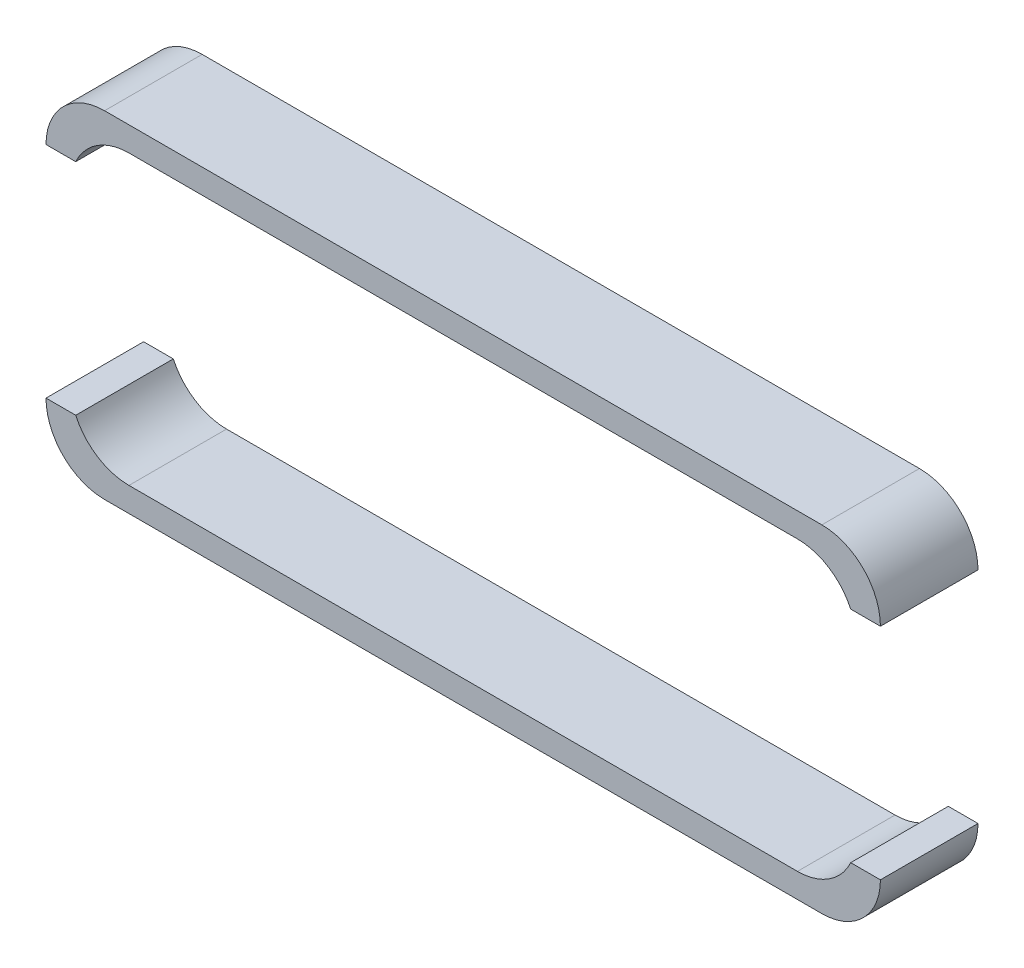
SolidWorks part; units mm, degrees
ref_plane "Plan de face" through (0, 0, 0) normal (0, 0, 1) x (1, 0, 0)
ref_plane "Plan de dessus" through (0, 0, 0) normal (0, 1, 0) x (1, 0, 0)
ref_plane "Plan de droite" through (0, 0, 0) normal (1, 0, 0) x (0, 0, -1)
sketch "Esquisse1" plane through (0, 0, 0) normal (0, 0, 1) x (1, 0, 0)
  line L1 (0, 0) -> (80.5, 0)
  line L2 (0, 0) -> (0, 29.5)
  line L3 (0, 29.5) -> (80.5, 29.5)
  line L4 (80.5, 0) -> (80.5, 29.5)
  line L5 (-2.5, -2.5) -> (83, -2.5)
  line L6 (-2.5, -2.5) -> (-2.5, 32)
  line L7 (-2.5, 32) -> (83, 32)
  line L8 (83, -2.5) -> (83, 32)
  dimension "D1" = 80.5
  dimension "D2" = 29.5
  dimension "D3" = 85.5
  dimension "D4" = 2.5
  dimension "D5" = 34.5
  dimension "D6" = 2.5
extrude "Boss.-Extru.1" add sketch "Esquisse1" along normal blind 10
fillet "Congé1" radius 6 4 edges at (80.5, 0, 5) (80.5, 29.5, 5) (0, 0, 5) (0, 29.5, 5)
fillet "Congé2" radius 6 4 edges at (83, 32, 5) (83, -2.5, 5) (-2.5, -2.5, 5) (-2.5, 32, 5)
sketch "Esquisse3" plane through (83, 0, 0) normal (1, 0, 0) x (0, 0, -1)
  line L1 (0, 26) -> (-10, 26)
  line L2 (0, 26) -> (0, 3.5)
  line L3 (0, 3.5) -> (-10, 3.5)
  line L4 (-10, 26) -> (-10, 3.5)
extrude "Enlèv. mat.-Extru.1" cut sketch "Esquisse3" against normal through all
